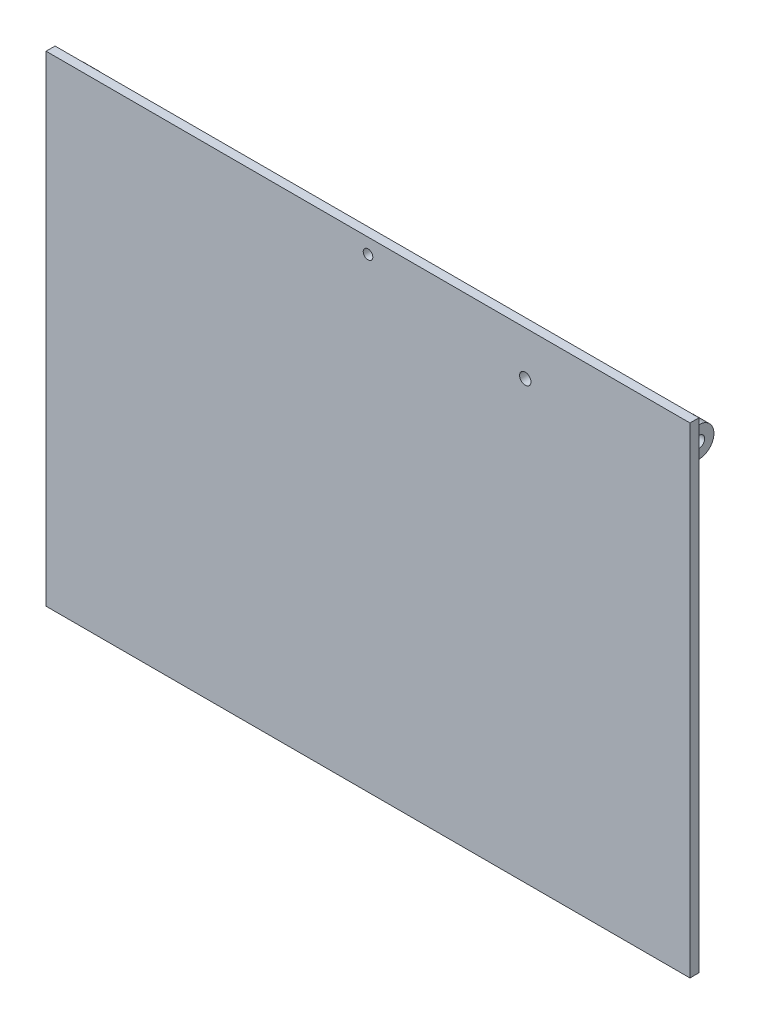
SolidWorks part; units mm, degrees
ref_plane "Płaszczyzna przednia" through (0, 0, 0) normal (0, 0, 1) x (1, 0, 0)
ref_plane "Płaszczyzna górna" through (0, 0, 0) normal (0, 1, 0) x (1, 0, 0)
ref_plane "Płaszczyzna prawa" through (0, 0, 0) normal (1, 0, 0) x (0, 0, -1)
sketch "Szkic1" plane through (0, 0, 0) normal (0, 0, 1) x (1, 0, 0)
  line L1 (0, 0) -> (215, 0)
  line L2 (0, 0) -> (0, 160.5)
  line L3 (0, 160.5) -> (215, 160.5)
  line L4 (215, 0) -> (215, 160.5)
  dimension "D1" = 215
  dimension "D2" = 160.5
extrude "Dodanie-wyciągnięcie1" add sketch "Szkic1" along normal blind 3
sketch "Szkic2" plane through (215, 0, 0) normal (1, 0, 0) x (0, 0, -1)
  line L0 (0, 0) -> (0, 160.5) construction
  line L1 (0, 155.5) -> (3, 155.5)
  line L2 (0, 155.5) -> (0, 145.5)
  line L3 (0, 145.5) -> (3, 145.5)
  arc A0 (3, 145.5) -> (3, 155.5) centre (3, 150.5) ccw
  circle A1 centre (3, 150.5) radius 1.9
  dimension "D1" = 5
  dimension "D4" = 3.8
  dimension "D2" = 10
  dimension "D3" = 5
  dimension "D5" = 3
extrude "Dodanie-wyciągnięcie2" add sketch "Szkic2" against normal blind 5 from offset 3 offset against normal yes
ref_plane "Płaszczyzna1" through (107.5, 0, 0) normal (-1, 0, 0) x (0, 0, 1)
mirror "Lustro1" about plane through (107.5, 0, 0) normal (-1, 0, 0) of "Dodanie-wyciągnięcie2"
sketch "Szkic3" plane through (0, 0, 0) normal (0, -1, 0) x (1, 0, 0)
  line L0 (0, 0) -> (215, 0) construction
  line L1 (10, 0) -> (20, 0)
  line L2 (10, 0) -> (10, -3)
  line L4 (20, 0) -> (20, -3)
  arc A0 (10, -3) -> (20, -3) centre (15, -3) ccw
  circle A1 centre (15, -3) radius 1.9
  dimension "D3" = 5
  dimension "D4" = 3.8
  dimension "D1" = 10
  dimension "D2" = 3
  dimension "D5" = 10
extrude "Dodanie-wyciągnięcie3" add sketch "Szkic3" against normal blind 5 from offset 3 offset against normal yes
mirror "Lustro2" about plane through (107.5, 0, 0) normal (-1, 0, 0) of "Dodanie-wyciągnięcie3"
chamfer "Sfazowanie1" distance 3 angle 45 4 edges at (195, 5.5, 0) (20, 5.5, 0) (5.5, 145.5, 0) (209.5, 145.5, 0)
chamfer "Sfazowanie2" distance 8 angle 10 4 edges at (16.5, 8, 0) (198.5, 8, 0) (8, 149, 0) (207, 149, 0) first distance on face at (15, 8, -4.9) first distance on face at (199.25, 8, -2.75) first distance on face at (8, 149.75, -2.75) first distance on face at (207, 150.5, -4.9)
sketch "Szkic4" plane through (0, 0, 0) normal (0, 0, -1) x (-1, 0, 0)
  line L0 (-215, 80.25) -> (0, 80.25)
  line L1 (-215, 0) -> (-215, 160.5) construction
  line L2 (0, 160.5) -> (0, 0) construction
  circle A1 centre (-107.5, 155.5) radius 1.6
  point P10 (-100.4026, 5)
  point P11 (0, 0)
  point P12 (0, 0)
extrude "Wytnij-wyciągnięcie1" cut sketch "Szkic4" against normal blind 10 contours A1 region at (107.5, 155.5, 0)
sketch "Szkic5" plane through (0, 0, 0) normal (0, 0, -1) x (-1, 0, 0)
  line L0 (-107.5, 0) -> (-107.5, 46.8676) construction
  line L1 (0, 0) -> (-215, 0) construction
  line L3 (-117.5, 3) -> (-97.5, 3)
  line L4 (-117.5, 3) -> (-117.5, 8)
  line L5 (-117.5, 8) -> (-97.5, 8)
  line L6 (-97.5, 3) -> (-97.5, 8)
  point P8 (-107.5, 8)
  point P9 (0, 0)
  dimension "D1" = 5
  dimension "D2" = 20
  dimension "D3" = 3
extrude "Dodanie-wyciągnięcie4" add sketch "Szkic5" along normal blind 35
sketch "Szkic6" plane through (0, 8, 0) normal (0, 1, 0) x (1, 0, 0)
  line L0 (215, 0) -> (0, 0) construction
  circle A0 centre (107.5, 15) radius 1.9
  dimension "D1" = 3.8
  dimension "D2" = 15
extrude "Wytnij-wyciągnięcie2" cut sketch "Szkic6" against normal blind 35
chamfer "Sfazowanie3" distance 2 angle 45 3 edges at (117.5, 5.5, 0) (107.5, 8, 0) (97.5, 5.5, 0)
sketch "Szkic7" plane through (0, 0, 0) normal (0, 0, -1) x (-1, 0, 0)
  line L0 (-215, 0) -> (-215, 160.5) construction
  line L1 (-165, 150.8) -> (-155, 150.8)
  line L2 (-165, 150.8) -> (-165, 140.8)
  line L3 (-165, 140.8) -> (-155, 140.8)
  line L4 (-155, 150.8) -> (-155, 140.8)
  line L5 (-215, 160.5) -> (0, 160.5) construction
  dimension "D1" = 10
  dimension "D2" = 50
  dimension "D3" = 9.7
extrude "Dodanie-wyciągnięcie5" add sketch "Szkic7" along normal blind 2
sketch "Szkic8" plane through (0, 0, -2) normal (0, 0, -1) x (-1, 0, 0)
  line L0 (-165, 150.8) -> (-155, 140.8) construction
  line L2 (-155, 150.8) -> (-165, 140.8) construction
  circle A0 centre (-160, 145.8) radius 1.9
  point P10 (0, 0)
  dimension "D1" = 3.8
extrude "Wytnij-wyciągnięcie3" cut sketch "Szkic8" against normal through all
